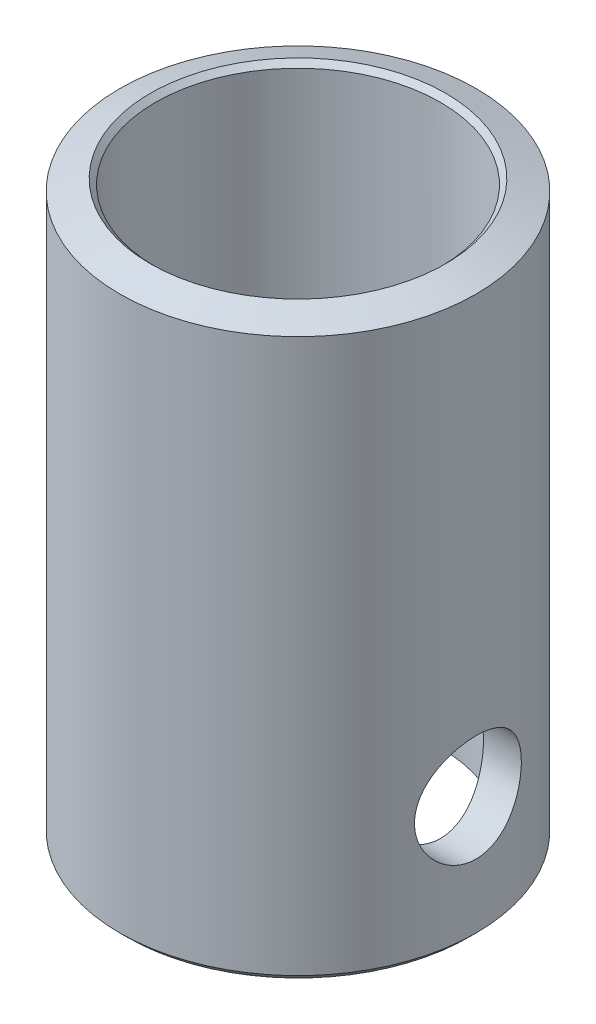
SolidWorks part; units mm, degrees
material "1060 Alloy"
ref_plane "Front Plane" through (0, 0, 0) normal (0, 0, 1) x (1, 0, 0)
ref_plane "Top Plane" through (0, 0, 0) normal (0, 1, 0) x (1, 0, 0)
ref_plane "Right Plane" through (0, 0, 0) normal (1, 0, 0) x (0, 0, -1)
sketch "Sketch1" plane through (0, 0, 0) normal (0, 1, 0) x (1, 0, 0)
  circle A0 centre (0, 0) radius 5
  circle A1 centre (0, 0) radius 4
  dimension "D1" = 10
  dimension "D2" = 8
extrude "Boss-Extrude1" add sketch "Sketch1" along normal blind 16.1
chamfer "Chamfer1" distance 0.2 angle 45 3 edges at (0, 0, 4) (0, 0, 5) (0, 16.1, 4)
chamfer "Chamfer2" distance 1 angle 20 1 edges at (0, 16.1, 5) first distance on face at (0, 16.1, 4.2)
ref_plane "Plane1" through (0, 0, -5) normal (0, 0, -1) x (-1, 0, 0)
sketch "Sketch2" plane through (0, 0, -5) normal (0, 0, -1) x (-1, 0, 0)
  line L0 (0, 0) -> (0, 3.5) construction
  circle A0 centre (0, 3.5) radius 1.5
  dimension "D2" = 3
  dimension "D1" = 3.5
extrude "Cut-Extrude1" cut sketch "Sketch2" against normal up to next
ref_axis "Axis1" through (0, 15.9, 0) along (0, -1, 0)
pattern_circular "CirPattern1" count 2 every 90 about axis through (0, 15.9, 0) along (0, -1, 0) of "Cut-Extrude1"
